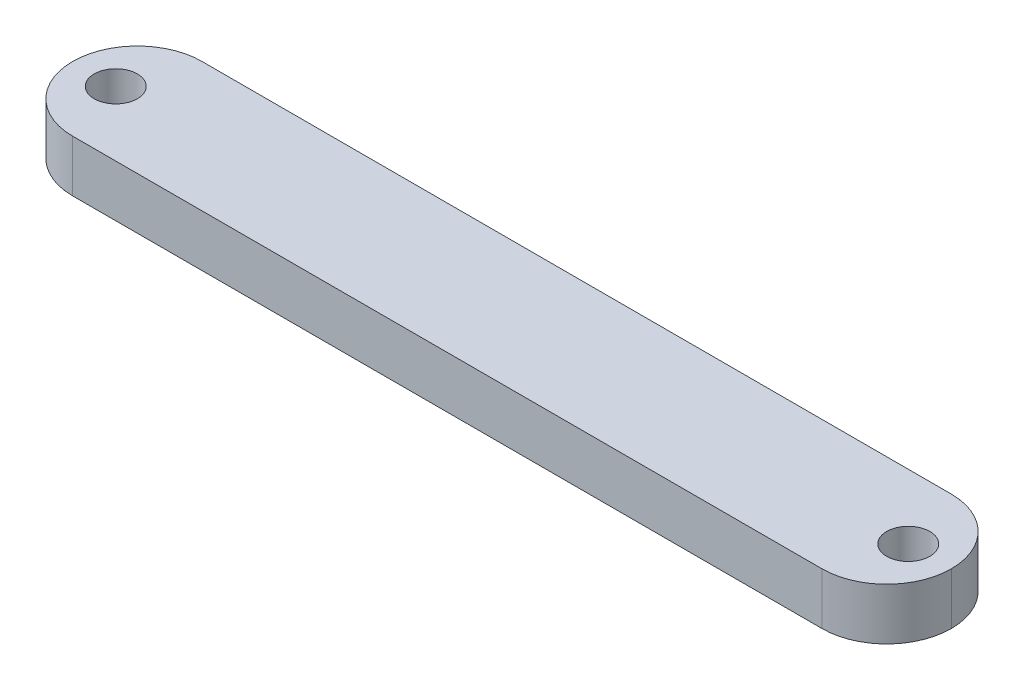
SolidWorks part; units mm, degrees
ref_plane "Front Plane" through (0, 0, 0) normal (0, 0, 1) x (1, 0, 0)
ref_plane "Top Plane" through (0, 0, 0) normal (0, 1, 0) x (1, 0, 0)
ref_plane "Right Plane" through (0, 0, 0) normal (1, 0, 0) x (0, 0, -1)
sketch "Sketch1" plane through (0, 0, 0) normal (0, 1, 0) x (1, 0, 0)
  line L1 (0, 0) -> (101.88, 0)
  line L2 (0, 0) -> (0, 15)
  line L3 (0, 15) -> (101.88, 15)
  line L4 (101.88, 0) -> (101.88, 15)
  circle A0 centre (5, 7.5) radius 2.5
  circle A1 centre (96.88, 7.5) radius 2.5
  dimension "D2" = 5
  dimension "D3" = 5
  dimension "D6" = 5
  dimension "D1" = 15
  dimension "D4" = 5
  dimension "D5" = 7.5
  dimension "D7" = 7.5
  dimension "D8" = 91.88
extrude "Boss-Extrude1" add sketch "Sketch1" along normal blind 6
fillet "Fillet1" radius 7.5 4 edges at (101.88, 3, 0) (101.88, 3, -15) (0, 3, -15) (0, 3, 0)
